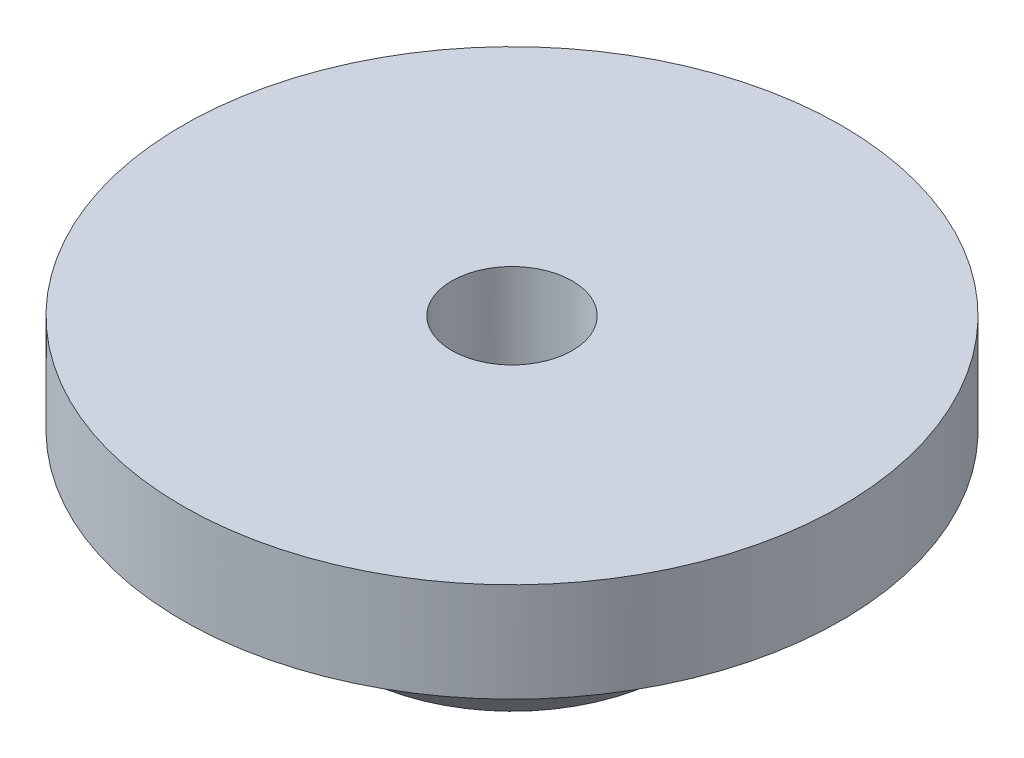
SolidWorks part; units mm, degrees
ref_plane "Front Plane" through (0, 0, 0) normal (0, 0, 1) x (1, 0, 0)
ref_plane "Top Plane" through (0, 0, 0) normal (0, 1, 0) x (1, 0, 0)
ref_plane "Right Plane" through (0, 0, 0) normal (1, 0, 0) x (0, 0, -1)
sketch "Sketch1" plane through (0, 0, 0) normal (0, 1, 0) x (1, 0, 0)
  circle A0 centre (0, 0) radius 22.45
  circle A1 centre (0, 0) radius 1.4
  dimension "D1" = 44.9
  dimension "D2" = 2.8
extrude "Boss-Extrude1" add sketch "Sketch1" along normal blind 2.3
sketch "Sketch2" plane through (0, 2.3, 0) normal (0, 1, 0) x (1, 0, 0)
  circle A0 centre (0, 0) radius 4.15
  circle A1 centre (0, 0) radius 5.8
  dimension "D1" = 11.6
  dimension "D2" = 8.3
extrude "Boss-Extrude2" [suppressed] add sketch "Sketch2" along normal blind 1.15
chamfer "Chamfer1" [suppressed] distance 1.15 angle 45
sketch "Sketch3" plane through (0, 2.3, 0) normal (0, 1, 0) x (1, 0, 0)
  circle A1 centre (0, 0) radius 22.45
  circle A3 centre (0, 0) radius 22.45
  dimension "D1" = 0
extrude "Cut-Extrude1" [suppressed] cut sketch "Sketch3" against normal blind 2.5 from surface
sketch "Sketch4" plane through (0, 0, 0) normal (0, -1, 0) x (1, 0, 0)
  circle A0 centre (0, 0) radius 5.725
  circle A1 centre (0, 0) radius 1.4
  dimension "D1" = 11.45
extrude "Boss-Extrude3" add sketch "Sketch4" along normal blind 1.2
chamfer "Chamfer2" distance 1.2 angle 45 1 edges at (0, 0, 5.725)
sketch "Sketch5" plane through (0, -1.2, 0) normal (0, -1, 0) x (1, 0, 0)
  circle A0 centre (0, 0) radius 3.75
  circle A1 centre (0, 0) radius 1.4
  dimension "D1" = 7.5
extrude "Boss-Extrude4" add sketch "Sketch5" along normal blind 3 from surface starting at face at (0, 0, 6.925)
chamfer "Chamfer3" distance 1.8 angle 45 1 edges at (0, -1.2, -3.75)
sketch "Sketch6" plane through (0, -3, 0) normal (0, -1, 0) x (1, 0, 0)
  circle A0 centre (0, 0) radius 4.925
  dimension "D1" = 9.85
extrude "Cut-Extrude-Thin1" cut sketch "Sketch6" against normal up to surface (1.8 mm away) thin up to face at (0, -1.2, -5.55) thin type one direction wall 2
sketch "Sketch7" plane through (0, -3, 0) normal (0, -1, 0) x (1, 0, 0)
  line L0 (0, 2.85) -> (-0.3337, 2.5349)
  line L1 (0, 2.85) -> (0.3337, 2.5349)
  line L3 (0, 0) -> (0, 1.6313) construction
  line L5 (0.7376, 2.7529) -> (0.9784, 2.3621)
  line L6 (0.7376, 2.7529) -> (0.3337, 2.5349)
  line L8 (1.425, 2.4682) -> (1.5564, 2.0284)
  line L9 (1.425, 2.4682) -> (0.9784, 2.3621)
  line L11 (2.0153, 2.0153) -> (2.0284, 1.5564)
  line L12 (2.0153, 2.0153) -> (1.5564, 2.0284)
  line L14 (2.4682, 1.425) -> (2.3621, 0.9784)
  line L15 (2.4682, 1.425) -> (2.0284, 1.5564)
  line L17 (2.7529, 0.7376) -> (2.5349, 0.3337)
  line L18 (2.7529, 0.7376) -> (2.3621, 0.9784)
  line L20 (2.85, 0) -> (2.5349, -0.3337)
  line L21 (2.85, 0) -> (2.5349, 0.3337)
  line L23 (2.7529, -0.7376) -> (2.3621, -0.9784)
  line L24 (2.7529, -0.7376) -> (2.5349, -0.3337)
  line L26 (2.4682, -1.425) -> (2.0284, -1.5564)
  line L27 (2.4682, -1.425) -> (2.3621, -0.9784)
  line L29 (2.0153, -2.0153) -> (1.5564, -2.0284)
  line L30 (2.0153, -2.0153) -> (2.0284, -1.5564)
  line L32 (1.425, -2.4682) -> (0.9784, -2.3621)
  line L33 (1.425, -2.4682) -> (1.5564, -2.0284)
  line L35 (0.7376, -2.7529) -> (0.3337, -2.5349)
  line L36 (0.7376, -2.7529) -> (0.9784, -2.3621)
  line L38 (0, -2.85) -> (-0.3337, -2.5349)
  line L39 (0, -2.85) -> (0.3337, -2.5349)
  line L41 (-0.7376, -2.7529) -> (-0.9784, -2.3621)
  line L42 (-0.7376, -2.7529) -> (-0.3337, -2.5349)
  line L44 (-1.425, -2.4682) -> (-1.5564, -2.0284)
  line L45 (-1.425, -2.4682) -> (-0.9784, -2.3621)
  line L47 (-2.0153, -2.0153) -> (-2.0284, -1.5564)
  line L48 (-2.0153, -2.0153) -> (-1.5564, -2.0284)
  line L50 (-2.4682, -1.425) -> (-2.3621, -0.9784)
  line L51 (-2.4682, -1.425) -> (-2.0284, -1.5564)
  line L53 (-2.7529, -0.7376) -> (-2.5349, -0.3337)
  line L54 (-2.7529, -0.7376) -> (-2.3621, -0.9784)
  line L56 (-2.85, 0) -> (-2.5349, 0.3337)
  line L57 (-2.85, 0) -> (-2.5349, -0.3337)
  line L59 (-2.7529, 0.7376) -> (-2.3621, 0.9784)
  line L60 (-2.7529, 0.7376) -> (-2.5349, 0.3337)
  line L62 (-2.4682, 1.425) -> (-2.0284, 1.5564)
  line L63 (-2.4682, 1.425) -> (-2.3621, 0.9784)
  line L65 (-2.0153, 2.0153) -> (-1.5564, 2.0284)
  line L66 (-2.0153, 2.0153) -> (-2.0284, 1.5564)
  line L68 (-1.425, 2.4682) -> (-0.9784, 2.3621)
  line L69 (-1.425, 2.4682) -> (-1.5564, 2.0284)
  line L71 (-0.7376, 2.7529) -> (-0.3337, 2.5349)
  line L72 (-0.7376, 2.7529) -> (-0.9784, 2.3621)
  point P78 (0, 0)
  dimension "D2" = 93.28
  dimension "D4" = 24
extrude "Cut-Extrude4" cut sketch "Sketch7" against normal blind 3
sketch "Sketch8" plane through (0, 2.3, 0) normal (0, 1, 0) x (1, 0, 0)
  line L0 (0, 0) -> (12.3037, 12.3037) construction
  line L1 (0, 0) -> (0, 19.35) construction
  line L2 (0, 0) -> (-11.1845, 13.3292) construction
  line L3 (0, 0) -> (-12.3037, -12.3037) construction
  line L4 (0, 0) -> (13.3292, -11.1845) construction
  line L5 (0, 0) -> (0, -19.35) construction
  line L6 (0, 0) -> (-19.2764, 1.6865) construction
  line L8 (19.2764, 1.6865) -> (0, 0) construction
  circle A0 centre (0, 0) radius 19.35 construction
  circle A1 centre (0, 0) radius 17.4 construction
  circle A2 centre (0, 19.35) radius 0.75
  circle A4 centre (-19.2764, 1.6865) radius 0.75
  circle A5 centre (-12.3037, -12.3037) radius 0.75
  circle A6 centre (0, -19.35) radius 0.75
  circle A7 centre (13.3292, -11.1845) radius 0.75
  circle A8 centre (19.2764, 1.6865) radius 0.75
  circle A9 centre (12.3037, 12.3037) radius 0.75
  circle A10 centre (-11.1845, 13.3292) radius 0.75
  point P17 (0, 0)
  point P24 (0, 0)
  dimension "D1" = 34.8
  dimension "D2" = 38.7
  dimension "D4" = 1.5
  dimension "D5" = 85
  dimension "D3" = 45
  dimension "D6" = 85
  dimension "D7" = 85
  dimension "D8" = 85
extrude "Cut-Extrude5" [suppressed] cut sketch "Sketch8" against normal up to next
sketch "Sketch9" [suppressed] plane through (0, 2.3, 0) normal (0, 1, 0) x (1, 0, 0)
  circle A2 centre (0, 0) radius 12.4
  circle A3 centre (0, 0) radius 12.6
  circle A4 centre (0, 0) radius 17.3
  circle A5 centre (0, 0) radius 17.5
  circle A6 centre (0, 0) radius 19.45
  circle A7 centre (0, 0) radius 19.25
  circle A8 centre (0, 0) radius 12.5 construction
  circle A9 centre (0, 0) radius 17.4 construction
  circle A10 centre (0, 0) radius 19.35 construction
  point P17 (-11.1845, 13.3292)
  point P19 (0, 19.35)
  circle M7 centre (0, 19.35) radius 0.75
  circle M8 centre (-11.1845, 13.3292) radius 0.75
  circle M9 centre (12.3037, 12.3037) radius 0.75
  circle M10 centre (19.2764, 1.6865) radius 0.75
  circle M11 centre (13.3292, -11.1845) radius 0.75
  circle M12 centre (0, -19.35) radius 0.75
  circle M13 centre (-12.3037, -12.3037) radius 0.75
  circle M14 centre (-19.2764, 1.6865) radius 0.75
  dimension "D1" = 0.2
  dimension "D2" = 0.2
  dimension "D3" = 0.2
  dimension "D4" = 0.1
  dimension "D5" = 0.1
  dimension "D6" = 0.1
  dimension "D7" = 25
extrude "Cut-Extrude6" [suppressed] cut sketch "Sketch9" against normal blind 0.2 contours A5 A4 M11 M9 | A7 A6 M10 M7 | A3 A2 | A5 A4 M9 M8 | A7 A6 M7 M14 | A7 A6 M14 M12 | A5 A4 M8 M13 | A7 A6 M12 M10 | A5 A4 M13 M11
sketch "Sketch10" [suppressed] plane through (0, 2.3, 0) normal (0, 1, 0) x (1, 0, 0)
  line L0 (-20.1291, 4.705) -> (-2.7185, 9.6234)
  line L1 (2.7381, 9.6178) -> (20.1252, 4.668)
  line L2 (-20.6403, -1.1382) -> (-4.3483, -9.0051)
  line L3 (4.3666, -8.9963) -> (20.63, -1.1024)
  line L4 (-20.1835, 4.8975) -> (-2.7729, 9.8159)
  line L5 (2.7928, 9.8102) -> (20.1799, 4.8604)
  line L6 (4.4539, -9.1762) -> (20.7173, -1.2823)
  line L7 (-20.7273, -1.3183) -> (-4.4353, -9.1852)
  arc A0 (-20.1291, 4.705) -> (-20.6403, -1.1382) centre (-19.2764, 1.6865) ccw
  arc A1 (20.63, -1.1024) -> (20.1252, 4.668) centre (19.2764, 1.6865) ccw
  arc A2 (-4.3483, -9.0051) -> (4.3666, -8.9963) centre (0, 0) ccw
  arc A3 (2.7381, 9.6178) -> (-2.7185, 9.6234) centre (0, 0) ccw
  arc A4 (2.7928, 9.8102) -> (-2.7729, 9.8159) centre (0, 0) ccw
  arc A5 (20.7173, -1.2823) -> (20.1799, 4.8604) centre (19.2764, 1.6865) ccw
  arc A6 (-4.4353, -9.1852) -> (4.4539, -9.1762) centre (0, 0) ccw
  arc A7 (-20.1835, 4.8975) -> (-20.7273, -1.3183) centre (-19.2764, 1.6865) ccw
  dimension "D1" = 20
  dimension "D2" = 0.2
extrude "Cut-Extrude7" [suppressed] cut sketch "Sketch10" against normal blind 0.2
fillet "Fillet1" [suppressed] radius 0.05
sketch "Sketch11" plane through (0, 0, 0) normal (0, -1, 0) x (-1, 0, 0)
  circle A0 centre (0, 0) radius 7.6495
  circle A1 centre (0, 0) radius 31.474
extrude "Cut-Extrude8" cut sketch "Sketch11" against normal blind 10
